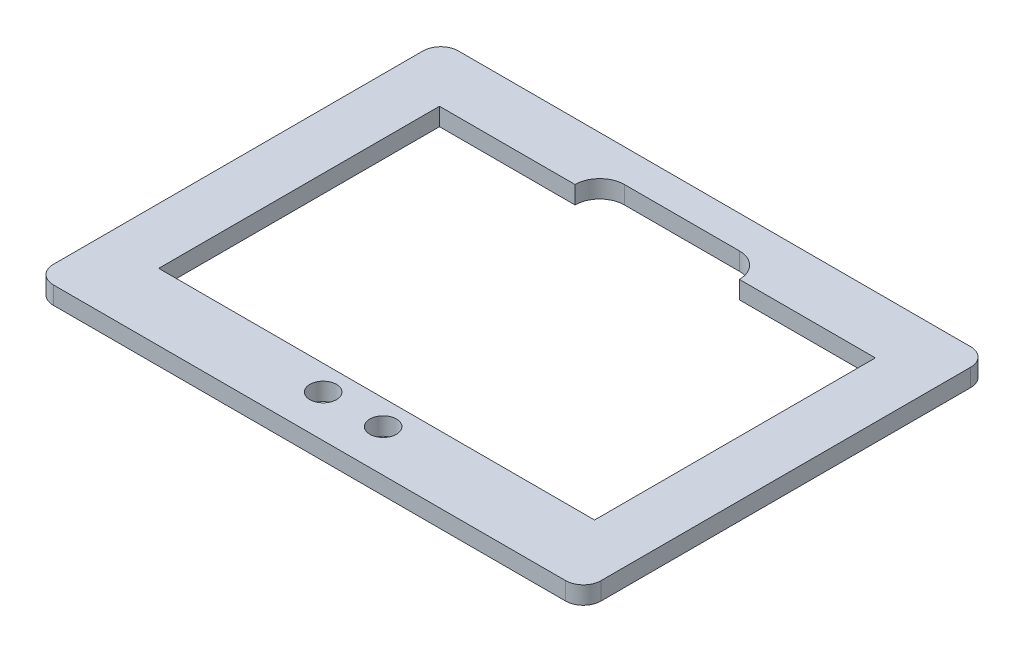
SolidWorks part; units mm, degrees
ref_plane "Front Plane" through (0, 0, 0) normal (0, 0, 1) x (1, 0, 0)
ref_plane "Top Plane" through (0, 0, 0) normal (0, 1, 0) x (1, 0, 0)
ref_plane "Right Plane" through (0, 0, 0) normal (1, 0, 0) x (0, 0, -1)
sketch "Sketch1" plane through (0, 0, 0) normal (0, 1, 0) x (1, 0, 0)
  line L28 (-39.5941, 29.2447) -> (38.9359, 29.2447)
  line L37 (-39.5941, 29.2447) -> (-39.5941, -28.8353)
  line L38 (-39.5941, -28.8353) -> (38.9359, -28.8353)
  line L39 (38.9359, 29.2447) -> (38.9359, -28.8353)
  line L40 (-31.5441, 21.0211) -> (30.9476, 21.0211)
  line L41 (-31.5441, 21.0211) -> (-31.5441, -19.2326)
  line L42 (-31.5441, -19.2326) -> (30.9476, -19.2326)
  line L43 (30.9476, 21.0211) -> (30.9476, -19.2326)
  circle A8 centre (-4.4022, -22.7972) radius 1.905
  circle A9 centre (4.1978, -22.7972) radius 1.905
  dimension "D1" = 3.81
extrude "Boss-Extrude1" add sketch "Sketch1" along normal blind 2.54
sketch "Sketch2" plane through (0, 2.54, 0) normal (0, 1, 0) x (1, 0, 0)
  line L0 (-8.5687, 21.0211) -> (7.9104, 21.0211) construction
  line L1 (30.9476, 21.0211) -> (-31.5441, 21.0211) construction
  line L2 (-8.5687, 24.5643) -> (7.9104, 24.5643)
  line L3 (-8.5687, 17.4779) -> (7.9104, 17.4779)
  line L4 (38.9359, 29.2447) -> (-39.5941, 29.2447) construction
  arc A0 (-8.5687, 24.5643) -> (-8.5687, 17.4779) centre (-8.5687, 21.0211) ccw
  arc A1 (7.9104, 17.4779) -> (7.9104, 24.5643) centre (7.9104, 21.0211) ccw
  point P4 (-0.3291, 21.0211)
  point P12 (-0.3291, 29.2447)
extrude "Cut-Extrude1" cut sketch "Sketch2" against normal blind 2.54
fillet "Fillet1" radius 2.54 4 edges at (38.9359, 1.27, -29.2447) (-39.5941, 1.27, -29.2447) (-39.5941, 1.27, 28.8353) (38.9359, 1.27, 28.8353)
